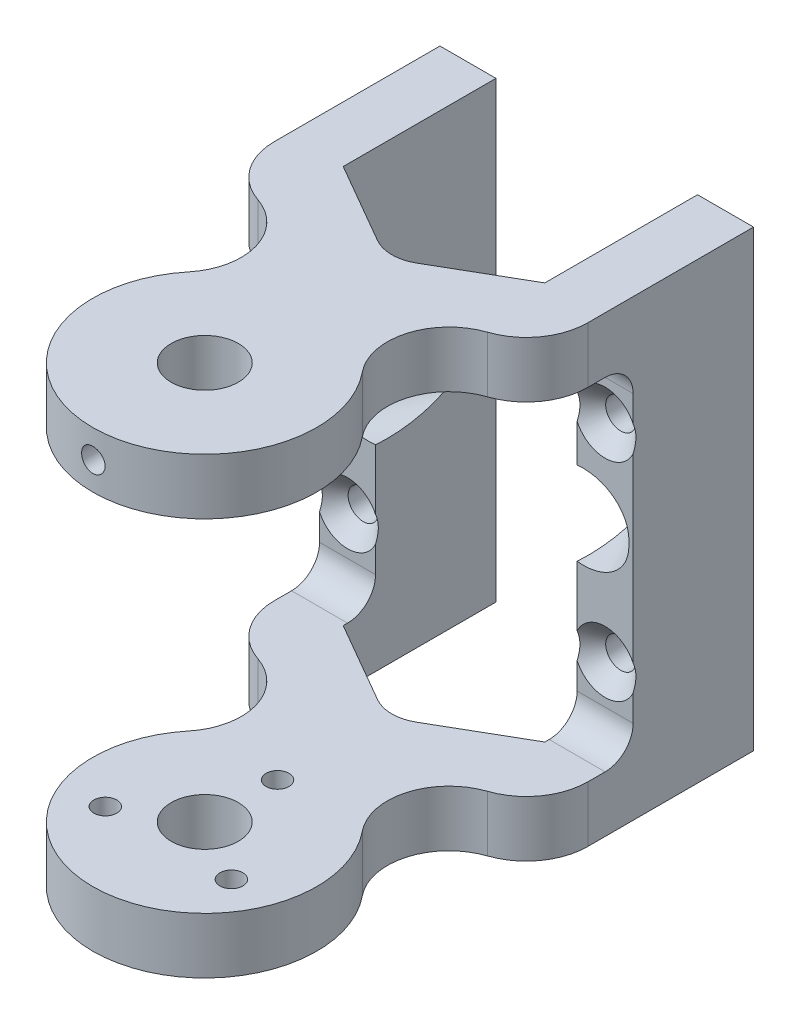
SolidWorks part; units mm, degrees
material "7075-T6 (SN)"
ref_plane "Face" through (0, 0, 0) normal (0, 0, 1) x (1, 0, 0)
ref_plane "Dessus" through (0, 0, 0) normal (0, 1, 0) x (1, 0, 0)
ref_plane "Droite" through (0, 0, 0) normal (1, 0, 0) x (0, 0, -1)
sketch "Esquisse3" plane through (0, 0, 0) normal (0, 1, 0) x (1, 0, 0)
  line L0 (-14, 0) -> (-14, -35)
  line L1 (0, 0) -> (0, -35) construction
  line L3 (14, -35) -> (14, 0)
  line L4 (-14, 0) -> (14, 0)
  line L6 (-14, 0) -> (-14, 3.841) construction
  line L7 (14, 0) -> (14, 6.0564) construction
  circle A0 centre (0, -35) radius 3
  arc A1 (-14, -35) -> (14, -35) centre (0, -35) ccw
  dimension "D2" = 6
  dimension "D1" = 28
  dimension "D4" = 35
extrude "Boss.-Extru.1" add sketch "Esquisse3" along normal mid plane 40.5
sketch "Esquisse5" plane through (0, 0, 0) normal (1, 0, 0) x (0, 0, -1)
  line L1 (-49, 15.25) -> (-24.5, 15.25)
  line L6 (-24.5, 15.25) -> (-24.5, -15.25)
  line L7 (-24.5, -15.25) -> (-49, -15.25)
  line L8 (-49, 20.25) -> (-49, -20.25) construction
  line L9 (-49, -15.25) -> (-49, 15.25)
  line L10 (-35, 20.25) -> (-49, 20.25) construction
  line L11 (-49, -20.25) -> (-35, -20.25) construction
  dimension "D1" = 5
  dimension "D2" = 5
  dimension "D3" = 24.5
extrude "Enlèv. mat.-Extru.2" cut sketch "Esquisse5" against normal through all and the other way through all
sketch "Esquisse6" plane through (0, 0, 0) normal (0, 1, 0) x (1, 0, 0)
  line L0 (-9, 0) -> (-9, -13.638)
  line L4 (-9, -13.638) -> (-1.75, -17.8238)
  line L6 (1.75, -17.8238) -> (9, -13.638)
  line L7 (14, -35) -> (14, 0) construction
  line L8 (9, -13.638) -> (9, 0)
  line L9 (9, 0) -> (-9, 0)
  line L11 (0, 0) -> (0, -14.7927) construction
  line L12 (0, -35) -> (14, -26.9171) construction
  line L13 (-14, 0) -> (-14, -35) construction
  arc A0 (-1.75, -17.8238) -> (1.75, -17.8238) centre (0, -14.7927) ccw
  dimension "D1" = 3.5
  dimension "D2" = 60
  dimension "D3" = 28
  dimension "D4" = 18
  dimension "D5" = 5
extrude "Enlèv. mat.-Extru.3" cut sketch "Esquisse6" against normal through all and the other way through all contours L4 A0 L6 L8 L9 L0 region at (0, 0, 8.1643)
sketch "Esquisse7" plane through (0, -15.25, 0) normal (0, 1, 0) x (1, 0, 0)
  line L0 (0, -35) -> (-21, -22.8756) construction
  line L1 (-7, -47.1244) -> (-28, -35)
  line L2 (-1.75, -17.8238) -> (-14, -10.7513)
  line L3 (0, -35) -> (21, -22.8756) construction
  line L4 (1.75, -17.8238) -> (14, -10.7513)
  line L5 (7, -47.1244) -> (28, -35)
  line L6 (0, 0) -> (0, -35) construction
  line L7 (-14, 0) -> (-14, -35) construction
  line L8 (14, -35) -> (14, 0) construction
  line L9 (1.75, -17.8238) -> (9, -13.638) construction
  line L10 (-9, -13.638) -> (-1.75, -17.8238) construction
  arc A0 (-1.75, -17.8238) -> (1.75, -17.8238) centre (0, -14.7927) ccw construction
  arc A1 (-14, -10.7513) -> (-28, -35) centre (-21, -22.8756) ccw
  arc A2 (-1.75, -17.8238) -> (1.75, -17.8238) centre (0, -14.7927) ccw
  arc A3 (28, -35) -> (14, -10.7513) centre (21, -22.8756) ccw
  arc A4 (-7, -47.1244) -> (7, -47.1244) centre (0, -35) ccw
  dimension "D1" = 60
extrude "Enlèv. mat.-Extru.4" cut sketch "Esquisse7" along normal up to surface (30.5 mm away) up to face at (0, 15.25, 38)
sketch "Esquisse8" plane through (0, 0, 0) normal (1, 0, 0) x (0, 0, -1)
  line L1 (-13.638, 15.25) -> (-10.7513, 15.25)
  line L2 (-13.638, 15.25) -> (-13.638, -15.25)
  line L3 (-13.638, -15.25) -> (-10.7513, -15.25)
  line L4 (-10.7513, 15.25) -> (-10.7513, -15.25)
extrude "Enlèv. mat.-Extru.5" cut sketch "Esquisse8" against normal through all and the other way through all
fillet "Congé1" radius 2.5 4 edges at (11.5, 15.25, 10.7513) (11.5, -15.25, 10.7513) (-11.5, 15.25, 10.7513) (-11.5, -15.25, 10.7513)
hole_wizard "Fraisage pour vis à tête fraisée M2.51" positions "Esquisse10" profile "Esquisse9" countersink size "M2.5" standard "DIN" end condition up to next
sketch "Esquisse10" plane through (0, 0, 10.7513) normal (0, 0, 1) x (1, 0, 0)
  line L1 (11.5, -9.25) -> (-11.5, -9.25)
  line L2 (11.5, -9.25) -> (11.5, 9.25)
  line L3 (11.5, 9.25) -> (-11.5, 9.25)
  line L4 (-11.5, -9.25) -> (-11.5, 9.25)
  line L5 (11.5, -9.25) -> (-11.5, 9.25) construction
  line L6 (11.5, 9.25) -> (-11.5, -9.25) construction
  line L7 (-11.5, 0) -> (-9, 0) construction
  line L8 (-9, 12.75) -> (-9, -12.75) construction
  line L11 (-11.5, 0) -> (-14, 0) construction
  line L12 (-14, 12.75) -> (-14, -12.75) construction
  line L13 (-14, -20.25) -> (14, -20.25) construction
  point P1 (0, 0)
  point P2 (-11.5, 9.25)
  point P91 (11.5, -9.25)
  point P92 (11.5, 9.25)
  point P93 (-11.5, -9.25)
  dimension "D1" = 11
sketch "Esquisse9" plane through (0, 0, 10.7513) normal (1, 0, 0) x (0, -1, 0)
  line L0 (0, 0) -> (0, 10.7513)
  line L1 (0, 10.7513) -> (1.35, 10.7513)
  line L2 (1.35, 10.7513) -> (1.35, 1.4)
  line L3 (1.35, 1.4) -> (2.75, 0)
  line L5 (2.75, 0) -> (0, 0)
  line L6 (-1.35, 1.4) -> (-2.75, 0) construction
  line L11 (0, -6.35) -> (0, 107.95) construction
  dimension "Diamètre du perçage jusqu'au prochain" = 2.7
  dimension "Profondeur du perçage jusqu'au prochain" = 10.7513
  dimension "Diamètre du fraisage entrant" = 5.5
  dimension "Angle du fraisage entrant" = 90
sketch "Esquisse11" plane through (0, -20.25, 0) normal (0, -1, 0) x (1, 0, 0)
  line L0 (0, 49) -> (0, 14.7927) construction
  line L1 (-14, 0) -> (-14, 35) construction
  line L3 (14, 14.7927) -> (14, 35)
  line L4 (14, 35) -> (14, 0) construction
  line L5 (-14, 14.7927) -> (14, 14.7927) construction
  line L6 (-14, 14.7927) -> (-14, 35)
  arc A0 (7.7551, 28.6866) -> (-7.7551, 28.6866) centre (0, 35) ccw
  arc A1 (-10.2602, 20.0035) -> (-14, 14.7927) centre (-8.5, 14.7927) ccw
  arc A2 (7.7551, 28.6866) -> (10.2602, 20.0035) centre (12.0203, 25.2142) ccw
  arc A3 (14, 35) -> (-14, 35) centre (0, 35) ccw construction
  arc A4 (14, 35) -> (-14, 35) centre (0, 35) ccw
  arc A5 (-7.7551, 28.6866) -> (-10.2602, 20.0035) centre (-12.0203, 25.2142) cw
  arc A6 (10.2602, 20.0035) -> (14, 14.7927) centre (8.5, 14.7927) cw
  arc A7 (1.75, 17.8238) -> (-1.75, 17.8238) centre (0, 14.7927) ccw construction
  dimension "D1" = 20
  dimension "D2" = 5.5
extrude "Enlèv. mat.-Extru.6" cut sketch "Esquisse11" against normal through all
hole_wizard "Trou taraudé M2.51" positions "Esquisse13" profile "Esquisse12" tap size "M2.5" standard "DIN" end condition up to next
sketch "Esquisse13" plane through (0, -20.25, 0) normal (0, 1, 0) x (1, 0, 0)
  line L0 (0, -28.5) -> (-5.6292, -38.25)
  line L1 (-5.6292, -38.25) -> (5.6292, -38.25)
  line L2 (5.6292, -38.25) -> (0, -28.5)
  line L4 (-3, -35) -> (-6.5, -35) construction
  circle A0 centre (0, -35) radius 6.5
  circle A1 centre (0, -35) radius 3 construction
  point P6 (0, -28.5)
  point P7 (-5.6292, -38.25)
  point P9 (5.6292, -38.25)
  dimension "D1" = 13
sketch "Esquisse12" plane through (0, -20.25, 28.5) normal (1, 0, 0) x (0, 0, -1)
  line L0 (0, 0) -> (0, 5)
  line L1 (0, 5) -> (1.025, 5)
  line L2 (1.025, 5) -> (1.025, 0)
  line L5 (1.025, 0) -> (0, 0)
  line L11 (0, -6.35) -> (0, 107.95) construction
  dimension "Diamètre du trou pour taraudage jusqu'au prochain" = 2.05
  dimension "Profondeur du trou pour taraudage jusqu'au prochain" = 5
cosmetic thread "Filetage de perçage1" parameters "D2"=2.5
cosmetic thread "Filetage de perçage2" parameters "D2"=2.5
cosmetic thread "Filetage de perçage3" parameters "D2"=2.5
ref_plane "Plan1" through (0, 0, 45) normal (0, 0, 1) x (1, 0, 0)
hole_wizard "Diamètre du perçage Ø2.1 (2.1)1" positions "Esquisse15" profile "Esquisse14" hole size "Ø2.1" standard "DIN"
sketch "Esquisse15" plane through (0, 0, 45) normal (0, 0, 1) x (1, 0, 0)
  line L0 (0, 20.25) -> (0, 15.25) construction
  line L4 (10, 20.25) -> (-10, 20.25) construction
  line L5 (-10, 15.25) -> (10, 15.25) construction
  point P0 (0, 17.75)
sketch "Esquisse14" plane through (0, 17.75, 45) normal (1, 0, 0) x (0, -1, 0)
  line L0 (0, 0) -> (0, 2.4309)
  line L1 (0, 2.4309) -> (1.05, 1.8)
  line L2 (1.05, 1.8) -> (1.05, 0)
  line L5 (1.05, 0) -> (0, 0)
  line L10 (0, 2.4309) -> (-1.05, 1.8) construction
  line L11 (0, -6.35) -> (0, 107.95) construction
  dimension "Diamètre du perçage" = 2.1
  dimension "Profondeur du perçage" = 1.8
  dimension "Angle de pointe" = 118
sketch "Esquisse19" plane through (8.1554, 0, 14.1256) normal (-0.5, 0, -0.866) x (-0.866, 0, 0.5)
  line L0 (-2.9186, 0.75) -> (-2.9186, 1.25) construction
  line L1 (7.3964, -20.25) -> (-0.9752, -20.25) construction
  line L2 (-6.4186, 0.75) -> (-6.4186, 1.25)
  line L3 (0.5814, 0.75) -> (0.5814, 1.25)
  line L5 (-2.4186, -8.1044) -> (-2.4186, 8.1044) construction
  arc A0 (-6.4186, 0.75) -> (0.5814, 0.75) centre (-2.9186, 0.75) ccw
  arc A1 (0.5814, 1.25) -> (-6.4186, 1.25) centre (-2.9186, 1.25) ccw
  point P4 (-2.9186, 1)
  dimension "D1" = 3.5
  dimension "D2" = 21
  dimension "D3" = 0.5
  dimension "D4" = 4
extrude "Enlèv. mat.-Extru.9" cut sketch "Esquisse19" against normal through all and the other way through all
mirror "Symétrie1" about plane through (0, 0, 0) normal (1, 0, 0) of "Enlèv. mat.-Extru.9"
